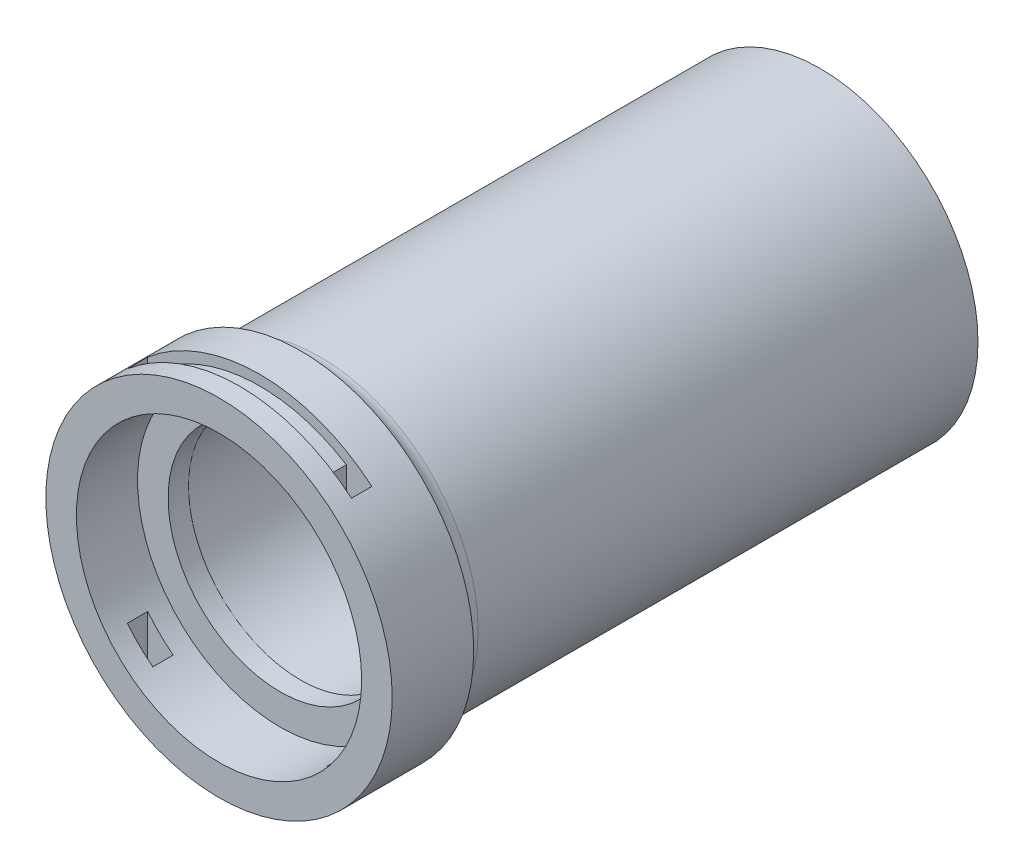
SolidWorks part; units mm, degrees
material "ABS"
ref_plane "Front Plane" through (0, 0, 0) normal (0, 0, 1) x (1, 0, 0)
ref_plane "Top Plane" through (0, 0, 0) normal (0, 1, 0) x (1, 0, 0)
ref_plane "Right Plane" through (0, 0, 0) normal (1, 0, 0) x (0, 0, -1)
sketch "Sketch1" plane through (0, 0, 0) normal (0, 0, 1) x (1, 0, 0)
  circle A0 centre (0, 0) radius 15.5
  dimension "D1" = 31
extrude "Boss-Extrude5" add sketch "Sketch1" along normal blind 26 contours A0
sketch "Sketch3" plane through (0, 0, 26) normal (0, 0, 1) x (1, 0, 0)
  circle A0 centre (0, 0) radius 5.625
  dimension "D1" = 11.25
extrude "Cut-Extrude2" cut sketch "Sketch3" against normal through all
sketch "Sketch4" plane through (0, 0, 26) normal (0, 0, 1) x (1, 0, 0)
  circle A0 centre (0, 0) radius 11.1125
  circle A2 centre (0, 0) radius 15.5 construction
  dimension "D1" = 22.225
  dimension "D2" = 4.3875
extrude "Cut-Extrude3" cut sketch "Sketch4" against normal blind 20 and the other way blind 28
sketch "Sketch7" plane through (0, 0, 0) normal (0, 0, 1) x (1, 0, 0)
  circle A1 centre (0, 0) radius 11
  circle A2 centre (0, 0) radius 9
  dimension "D1" = 18
  dimension "D2" = 22
extrude "Cut-Extrude6" cut sketch "Sketch7" against normal blind 2 from surface starting at face at (11.1125, 0, 6)
sketch "Sketch12" plane through (0, 0, 0) normal (0, 0, 1) x (1, 0, 0)
  circle A0 centre (0, 0) radius 17
  dimension "D1" = 34
extrude "Boss-Extrude8" add sketch "Sketch12" along normal up to surface (26 mm away) and the other way blind 2 from offset 20 up to face at (15.5, 0, 26)
sketch "Sketch13" plane through (0, 0, 0) normal (0, 0, 1) x (1, 0, 0)
  circle A0 centre (0, 0) radius 11
extrude "Cut-Extrude10" cut sketch "Sketch13" along normal through all from surface starting at face at (11.1125, 0, 18)
fillet "Fillet2" radius 2 1 edges at (15.5, 0, 18)
sketch "Sketch14" plane through (0, 0, 0) normal (0, 0, 1) x (1, 0, 0)
  circle A0 centre (0, 0) radius 14
  dimension "D1" = 28
extrude "Cut-Extrude11" cut sketch "Sketch14" against normal blind 6 from surface starting at face at (17, 0, 26)
sketch "Sketch15" plane through (0, 0, 0) normal (0, 0, 1) x (1, 0, 0)
  circle A0 centre (0, 10) radius 0.5
  circle A1 centre (0, 0) radius 11 construction
  circle A3 centre (0, -10) radius 0.5
  circle A4 centre (10, 0) radius 0.5
  circle A5 centre (-10, 0) radius 0.5
  dimension "D1" = 10
extrude "Cut-Extrude14" cut sketch "Sketch15" along normal through all contours A3 | A4 | A0 | A5
sketch "Sketch18" plane through (0, 0, 0) normal (0, 1, 0) x (1, 0, 0)
  line L0 (-17, -26) -> (17, -26) construction
  line L1 (11, -22) -> (-11, -22) construction
  line L2 (11, -22) -> (11, -24)
  line L3 (11, -24) -> (-11, -24) construction
  line L4 (-11, -22) -> (-11, -24)
  line L5 (11, -22) -> (-11, -24) construction
  line L6 (11, -24) -> (-11, -22) construction
  line L7 (-11, -24) -> (-8.5, -24)
  line L8 (-11, -24) -> (-11, -22)
  line L9 (-11, -22) -> (-8.5, -22)
  line L10 (-8.5, -24) -> (-8.5, -22)
  line L11 (11, -24) -> (8.5, -24)
  line L12 (11, -24) -> (11, -22)
  line L13 (11, -22) -> (8.5, -22)
  line L14 (8.5, -24) -> (8.5, -22)
  line L15 (-11, -22) -> (-8.5, -22)
  line L16 (-11, -24) -> (-8.5, -24)
  line L17 (8.5, -22) -> (11, -22)
  line L18 (8.5, -24) -> (11, -24)
  point P0 (0, -23)
  dimension "D1" = 2
  dimension "D2" = 2.5
  dimension "D3" = 2.5
  dimension "D4" = 17
  dimension "D5" = 0
  dimension "D6" = 2
extrude "Cut-Extrude15" cut sketch "Sketch18" against normal mid plane 40 contours L7 L10 L9 L4 | L14 L11 L2 L13 region at (9.75, 0, 23) region at (-9.75, 0, 23)
ref_plane "Plane1" through (0, 0, 24) normal (0, 0, -1) x (-1, 0, 0)
sketch "Sketch23" plane through (0, 0, 24) normal (0, 0, -1) x (-1, 0, 0)
  line L0 (9.7192, 13.9477) -> (9.1475, 13.1272)
  line L1 (-9.1475, 13.1272) -> (-9.7192, 13.9477)
  line L2 (-9.1475, -13.1272) -> (-9.7192, -13.9477)
  line L3 (9.7192, -13.9477) -> (9.1475, -13.1272)
  arc A0 (9.1475, 13.1272) -> (-9.1475, 13.1272) centre (0, 0) ccw
  arc A1 (9.1475, -13.1272) -> (-9.1475, -13.1272) centre (0, 0) cw
  arc A2 (9.7192, 13.9477) -> (-9.7192, 13.9477) centre (0, 0) ccw
  arc A3 (-9.7192, -13.9477) -> (9.7192, -13.9477) centre (0, 0) ccw
  dimension "D1" = 1
  dimension "D2" = 17
extrude "Cut-Extrude16" cut sketch "Sketch23" along normal blind 2
sketch "Sketch24" plane through (0, 0, 6) normal (0, 0, 1) x (1, 0, 0)
  circle A0 centre (0, 0) radius 9
  circle A1 centre (0, 0) radius 5.625
  dimension "D1" = 11.25
  dimension "D2" = 18
sketch "Sketch26" plane through (0, 0, 0) normal (0, 0, -1) x (-1, 0, 0)
  circle A0 centre (0, 0) radius 15.5
  circle A1 centre (0, 0) radius 5.625
  circle A2 centre (-10, 0) radius 0.5
  circle A3 centre (0, 10) radius 0.5
  circle A4 centre (10, 0) radius 0.5
  circle A5 centre (0, -10) radius 0.5
  point P16 (0, 0)
  dimension "D1" = 1
  dimension "D2" = 11.25
  dimension "D3" = 31
  dimension "D5" = 10
  dimension "D6" = 10
  dimension "D4" = 4
extrude "Boss-Extrude9" add sketch "Sketch26" along normal blind 33
